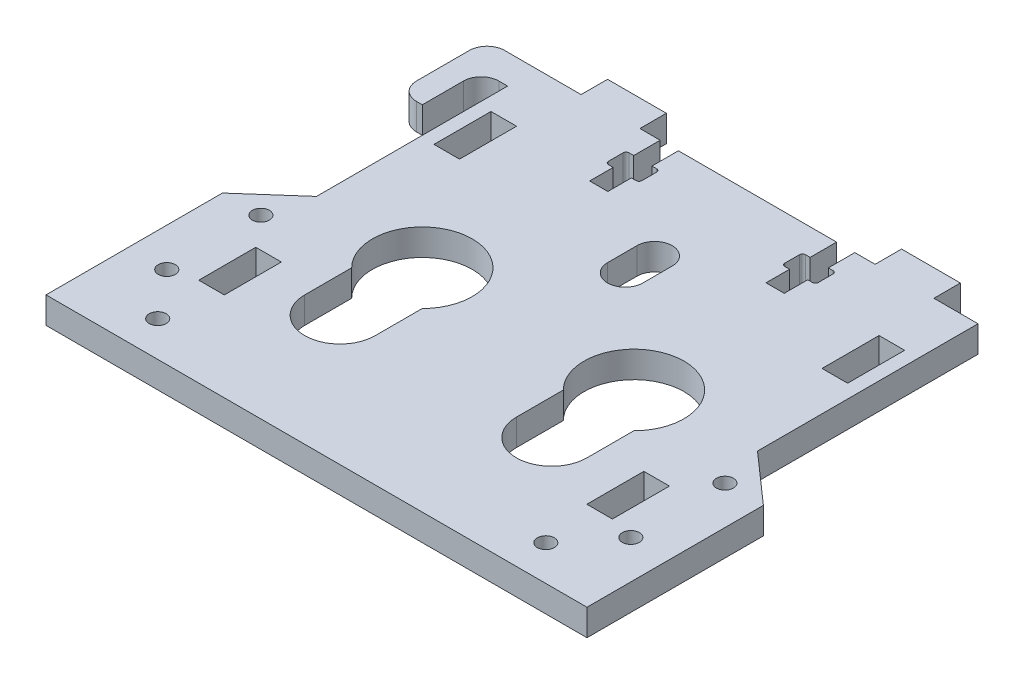
SolidWorks part; units mm, degrees
ref_plane "Front Plane" through (0, 0, 0) normal (0, 0, 1) x (1, 0, 0)
ref_plane "Top Plane" through (0, 0, 0) normal (0, 1, 0) x (1, 0, 0)
ref_plane "Right Plane" through (0, 0, 0) normal (1, 0, 0) x (0, 0, -1)
sketch "Sketch1" plane through (0, 0, 0) normal (0, 1, 0) x (1, 0, 0)
  line L1 (-37.5, 37.5) -> (37.5, 37.5)
  line L2 (-37.5, 37.5) -> (-37.5, -37.5)
  line L3 (-37.5, -37.5) -> (37.5, -37.5)
  line L4 (37.5, 37.5) -> (37.5, -37.5)
  line L5 (-37.5, 37.5) -> (37.5, -37.5) construction
  line L6 (-37.5, -37.5) -> (37.5, 37.5) construction
  point P0 (0, 0)
  dimension "D1" = 75
  dimension "D2" = 75
extrude "MainShape" add sketch "Sketch1" along normal blind 4.5
sketch "Sketch2" plane through (0, 4.5, 0) normal (0, 1, 0) x (1, 0, 0)
  line L0 (0, -37.5) -> (0, 37.5) construction
  line L1 (-37.5, -37.5) -> (37.5, -37.5) construction
  line L2 (37.5, 37.5) -> (-37.5, 37.5) construction
  line L4 (-5, 42) -> (5, 42)
  line L5 (-5, 42) -> (-5, 33)
  line L6 (-5, 33) -> (5, 33)
  line L7 (5, 42) -> (5, 33)
  line L8 (-5, 42) -> (5, 33) construction
  line L9 (-5, 33) -> (5, 42) construction
  dimension "D1" = 10
  dimension "D2" = 4.5
extrude "Tab1" [suppressed] add sketch "Sketch2" against normal through all
sketch "Sketch4" [suppressed] plane through (0, 4.5, 0) normal (0, 1, 0) x (1, 0, 0)
  line L0 (0, 42) -> (0, -37.5) construction
  line L1 (5, 42) -> (-5, 42) construction
  line L2 (-47.5, -37.5) -> (47.5, -37.5) construction
  line L3 (-40, 37.5) -> (-40, 27) construction
  line L4 (-5, 37.5) -> (-47.5, 37.5) construction
  line L5 (-38.25, 27) -> (-41.75, 27) construction
  line L6 (-41.75, 27) -> (-41.75, 37.5) construction
  line L7 (-38.25, 27) -> (-41.75, 27)
  line L8 (-41.75, 27) -> (-41.75, 29.5)
  line L9 (-41.75, 29.5) -> (-42.75, 29.5)
  line L10 (-43, 29.75) -> (-43, 33.45)
  line L11 (-42.75, 33.7) -> (-41.75, 33.7)
  line L12 (-41.75, 33.7) -> (-41.75, 37.5)
  line L13 (-41.75, 37.5) -> (-38.25, 37.5)
  line L14 (-38.25, 27) -> (-38.25, 37.5) construction
  line L15 (-38.25, 33.7) -> (-38.25, 37.5)
  line L16 (-37.25, 33.7) -> (-38.25, 33.7)
  line L17 (-37, 29.75) -> (-37, 33.45)
  line L18 (-38.25, 29.5) -> (-37.25, 29.5)
  line L19 (-38.25, 27) -> (-38.25, 29.5)
  line L20 (38.25, 27) -> (38.25, 37.5) construction
  line L21 (41.75, 27) -> (41.75, 37.5) construction
  line L22 (38.25, 27) -> (41.75, 27) construction
  line L23 (40, 37.5) -> (40, 27) construction
  line L24 (38.25, 27) -> (38.25, 29.5)
  line L25 (38.25, 29.5) -> (37.25, 29.5)
  line L26 (37, 29.75) -> (37, 33.45)
  line L27 (37.25, 33.7) -> (38.25, 33.7)
  line L28 (38.25, 33.7) -> (38.25, 37.5)
  line L29 (41.75, 37.5) -> (38.25, 37.5)
  line L30 (41.75, 33.7) -> (41.75, 37.5)
  line L31 (42.75, 33.7) -> (41.75, 33.7)
  line L32 (43, 29.75) -> (43, 33.45)
  line L33 (41.75, 29.5) -> (42.75, 29.5)
  line L34 (41.75, 27) -> (41.75, 29.5)
  line L35 (38.25, 27) -> (41.75, 27)
  arc A0 (-42.75, 29.5) -> (-43, 29.75) centre (-42.75, 29.75) cw
  arc A1 (-37, 29.75) -> (-37.25, 29.5) centre (-37.25, 29.75) cw
  arc A2 (-37.25, 33.7) -> (-37, 33.45) centre (-37.25, 33.45) cw
  arc A3 (-43, 33.45) -> (-42.75, 33.7) centre (-42.75, 33.45) cw
  arc A4 (43, 33.45) -> (42.75, 33.7) centre (42.75, 33.45) ccw
  arc A5 (37.25, 33.7) -> (37, 33.45) centre (37.25, 33.45) ccw
  arc A6 (37, 29.75) -> (37.25, 29.5) centre (37.25, 29.75) ccw
  arc A7 (42.75, 29.5) -> (43, 29.75) centre (42.75, 29.75) ccw
  point P24 (-43, 29.5)
  point P27 (-37, 29.5)
  point P30 (-37, 33.7)
  point P33 (-43, 33.7)
  point P56 (43, 33.7)
  point P57 (37, 33.7)
  point P58 (37, 29.5)
  point P59 (43, 29.5)
  dimension "D7" = 0.5
  dimension "D1" = 11
  dimension "D2" = 1.55
  dimension "D3" = 3.5
  dimension "D4" = 2.85
  dimension "D5" = 8
  dimension "D6" = 40
extrude "Cut-Extrude2" [suppressed] cut sketch "Sketch4" against normal through all
sketch "Sketch5" plane through (0, 4.5, 0) normal (0, 1, 0) x (1, 0, 0)
  line L0 (0, -37.5) -> (0, 37.5) construction
  line L1 (-37.5, -37.5) -> (37.5, -37.5) construction
  line L3 (33, 37.5) -> (33, -37.5) construction
  line L4 (37.5, 37.5) -> (-37.5, 37.5) construction
  line L5 (-33, 37.5) -> (-33, -37.5) construction
  line L6 (30.825, 27.35) -> (35.175, 27.35)
  line L7 (30.825, 27.35) -> (30.825, 17.65)
  line L8 (30.825, 17.65) -> (35.175, 17.65)
  line L9 (35.175, 27.35) -> (35.175, 17.65)
  line L10 (30.825, 27.35) -> (35.175, 17.65) construction
  line L11 (30.825, 17.65) -> (35.175, 27.35) construction
  line L12 (-30.825, 17.65) -> (-35.175, 27.35) construction
  line L13 (-30.825, 27.35) -> (-35.175, 17.65) construction
  line L14 (-35.175, 27.35) -> (-35.175, 17.65)
  line L15 (-30.825, 17.65) -> (-35.175, 17.65)
  line L16 (-30.825, 27.35) -> (-30.825, 17.65)
  line L17 (-30.825, 27.35) -> (-35.175, 27.35)
  line L18 (-37.5, 2.5) -> (37.5, 2.5) construction
  line L19 (-37.5, 37.5) -> (-37.5, -37.5) construction
  line L20 (37.5, -37.5) -> (37.5, 37.5) construction
  line L21 (-30.825, -22.35) -> (-35.175, -12.65) construction
  line L22 (-30.825, -12.65) -> (-35.175, -22.35) construction
  line L23 (30.825, -12.65) -> (35.175, -22.35) construction
  line L24 (30.825, -22.35) -> (35.175, -12.65) construction
  line L25 (-30.825, -22.35) -> (-35.175, -22.35)
  line L26 (-30.825, -22.35) -> (-30.825, -12.65)
  line L27 (-30.825, -12.65) -> (-35.175, -12.65)
  line L28 (-35.175, -22.35) -> (-35.175, -12.65)
  line L29 (35.175, -22.35) -> (35.175, -12.65)
  line L30 (30.825, -12.65) -> (35.175, -12.65)
  line L31 (30.825, -22.35) -> (30.825, -12.65)
  line L32 (30.825, -22.35) -> (35.175, -22.35)
  line L33 (-30.825, 27.35) -> (-35.175, 17.65) construction
  line L34 (-37.5, 37.5) -> (37.5, 37.5) construction
  line L35 (37.5, 37.5) -> (-37.5, 37.5) construction
  point P10 (33, 22.5)
  point P21 (-33, 22.5)
  point P36 (-33, -17.5)
  point P37 (33, -17.5)
  dimension "D1" = 33
  dimension "D2" = 9.7
  dimension "D3" = 4.35
  dimension "D4" = 15
  dimension "D5" = 40
extrude "Cut-Extrude3" cut sketch "Sketch5" against normal through all
sketch "Sketch6" plane through (0, 4.5, 0) normal (0, 1, 0) x (1, 0, 0)
  line L0 (-18, -37.5) -> (-18, 28) construction
  line L1 (-24, -15.5) -> (-24, -7.5208)
  line L3 (-37.5, -15.5) -> (37.5, -15.5) construction
  line L4 (-37.5, 37.5) -> (-37.5, -37.5) construction
  line L5 (37.5, -37.5) -> (37.5, 37.5) construction
  line L6 (37.5, 37.5) -> (-37.5, 37.5) construction
  line L7 (-37.5, -37.5) -> (37.5, -37.5) construction
  line L8 (-12, -15.5) -> (-12, -7.5208)
  line L9 (-37.5, 37.5) -> (37.5, 37.5) construction
  arc A0 (-24, -15.5) -> (-12, -15.5) centre (-18, -15.5) ccw
  arc A2 (-12, -7.5208) -> (-24, -7.5208) centre (-18, -1.5) ccw
  dimension "D1" = 12
  dimension "D6" = 8.5
  dimension "D2" = 53
  dimension "D3" = 0
  dimension "D5" = 0
  dimension "D7" = 14
  dimension "D4" = 18
extrude "Cut-Extrude4" cut sketch "Sketch6" against normal through all
sketch "Sketch13" plane through (0, 4.5, 0) normal (0, 1, 0) x (1, 0, 0)
  line L0 (-37.5, 0) -> (-46, -7.5)
  line L1 (-37.5, 37.5) -> (-37.5, -37.5) construction
  line L2 (-46, -7.5) -> (-46, -37.5)
  line L3 (-46, -37.5) -> (-37.5, -37.5)
  line L4 (-37.5, -37.5) -> (-37.5, 0)
  line L5 (0, 37.5) -> (0, -37.5) construction
  line L6 (37.5, 37.5) -> (-37.5, 37.5) construction
  line L7 (-37.5, -37.5) -> (37.5, -37.5) construction
  line L8 (37.5, -37.5) -> (37.5, 0)
  line L9 (46, -37.5) -> (37.5, -37.5)
  line L10 (46, -7.5) -> (46, -37.5)
  line L11 (37.5, 0) -> (46, -7.5)
  line L12 (-37.5, -37.5) -> (-37.5, 0)
  line M23 (37.5, -37.5) -> (37.5, 37.5)
  line M25 (-37.5, 37.5) -> (-37.5, -37.5)
  dimension "D1" = 46
  dimension "D2" = 30
extrude "Boss-Extrude2" add sketch "Sketch13" against normal through all contours L2 L3 L0 M25 | L11 L9 L10 M23 region at (-41.5926, 4.5, 20.5556) region at (41.5926, 4.5, 20.5556)
sketch "Sketch8" plane through (0, 4.5, 0) normal (0, 1, 0) x (1, 0, 0)
  line L0 (-18, -9.5) -> (-18, -21.5) construction
  line L1 (-18, -15.5) -> (-39.46, -15.5) construction
  line L2 (-39.46, -23.5) -> (-39.46, -7.5) construction
  line L3 (-18, -21.5) -> (-18, -9.5) construction
  circle A0 centre (-39.46, -7.5) radius 1.45
  circle A1 centre (-18, -15.5) radius 6 construction
  circle A2 centre (-39.46, -23.5) radius 1.45
  dimension "D3" = 2.9
  dimension "D1" = 0
  dimension "D2" = 8
  dimension "D4" = 21.46
extrude "Cut-Extrude6" cut sketch "Sketch8" against normal through all
mirror "Mirror1" about plane through (0, 0, 0) normal (1, 0, 0) of "Cut-Extrude6", "Cut-Extrude4"
sketch "Sketch11" plane through (0, 4.5, 0) normal (0, 1, 0) x (1, 0, 0)
  line L0 (0, 37.5) -> (0, -37.5) construction
  line L1 (37.5, 37.5) -> (-37.5, 37.5) construction
  line L2 (-46, -37.5) -> (46, -37.5) construction
  line L3 (-25, 42) -> (-25, 37.5) construction
  line L4 (-30, 37.5) -> (-20, 37.5)
  line L5 (-30, 37.5) -> (-30, 42)
  line L6 (-30, 42) -> (-20, 42)
  line L7 (-20, 37.5) -> (-20, 42)
  line L8 (25, 42) -> (25, 37.5) construction
  line L9 (20, 37.5) -> (20, 42)
  line L10 (30, 42) -> (20, 42)
  line L11 (30, 37.5) -> (30, 42)
  line L12 (30, 37.5) -> (20, 37.5)
  dimension "D1" = 10
  dimension "D2" = 4.5
  dimension "D3" = 25
extrude "RearTabs" add sketch "Sketch11" against normal through all
sketch "Sketch12" plane through (0, 4.5, 0) normal (0, 1, 0) x (1, 0, 0)
  line L0 (-15, 0) -> (-15, 37.5) construction
  line L1 (20, 37.5) -> (-20, 37.5) construction
  line L2 (-13.45, 37.5) -> (-16.55, 37.5)
  line L3 (-16.55, 37.5) -> (-16.55, 33)
  line L4 (-16.55, 33) -> (-17.35, 33)
  line L5 (-17.85, 32.5) -> (-17.85, 30)
  line L6 (-17.35, 29.5) -> (-16.55, 29.5)
  line L7 (-16.55, 29.5) -> (-16.55, 25.5)
  line L8 (-16.55, 25.5) -> (-13.45, 25.5)
  line L9 (-13.45, 29.5) -> (-13.45, 25.5)
  line L10 (-12.65, 29.5) -> (-13.45, 29.5)
  line L11 (-12.15, 32.5) -> (-12.15, 30)
  line L12 (-13.45, 33) -> (-12.65, 33)
  line L13 (-13.45, 37.5) -> (-13.45, 33)
  line L14 (0, 37.5) -> (0, 23.4067) construction
  line L15 (13.45, 37.5) -> (13.45, 33)
  line L16 (13.45, 33) -> (12.65, 33)
  line L17 (12.15, 32.5) -> (12.15, 30)
  line L18 (12.65, 29.5) -> (13.45, 29.5)
  line L19 (13.45, 29.5) -> (13.45, 25.5)
  line L20 (16.55, 25.5) -> (13.45, 25.5)
  line L21 (16.55, 29.5) -> (16.55, 25.5)
  line L22 (17.35, 29.5) -> (16.55, 29.5)
  line L23 (17.85, 32.5) -> (17.85, 30)
  line L24 (16.55, 33) -> (17.35, 33)
  line L25 (16.55, 37.5) -> (16.55, 33)
  line L26 (13.45, 37.5) -> (16.55, 37.5)
  arc A0 (-17.85, 30) -> (-17.35, 29.5) centre (-17.35, 30) ccw
  arc A1 (-17.35, 33) -> (-17.85, 32.5) centre (-17.35, 32.5) ccw
  arc A2 (-12.65, 33) -> (-12.15, 32.5) centre (-12.65, 32.5) cw
  arc A3 (-12.15, 30) -> (-12.65, 29.5) centre (-12.65, 30) cw
  arc A4 (12.15, 30) -> (12.65, 29.5) centre (12.65, 30) ccw
  arc A5 (12.65, 33) -> (12.15, 32.5) centre (12.65, 32.5) ccw
  arc A6 (17.35, 33) -> (17.85, 32.5) centre (17.35, 32.5) cw
  arc A7 (17.85, 30) -> (17.35, 29.5) centre (17.35, 30) cw
  point P14 (-17.85, 29.5)
  point P17 (-17.85, 33)
  point P25 (-15, 25.5)
  point P28 (-12.15, 33)
  point P29 (-12.15, 29.5)
  point P53 (12.15, 29.5)
  point P54 (12.15, 33)
  point P55 (15, 25.5)
  point P56 (17.85, 33)
  point P57 (17.85, 29.5)
  dimension "D5" = 8
  dimension "D1" = 12
  dimension "D6" = 0.5
  dimension "D2" = 3.5
  dimension "D3" = 2.85
  dimension "D4" = 1.55
  dimension "D7" = 15
extrude "FrontScrewSlot" cut sketch "Sketch12" against normal through all
sketch "Sketch14" plane through (0, 4.5, 0) normal (0, 1, 0) x (1, 0, 0)
  line L0 (-33, 27.35) -> (-33, -37.5) construction
  line L1 (-30.825, 27.35) -> (-35.175, 27.35) construction
  line L2 (-46, -37.5) -> (46, -37.5) construction
  line L3 (-30, 37.5) -> (-37.5, 37.5) construction
  line L4 (0, 0) -> (0, -37.5) construction
  line L5 (33, 27.35) -> (33, -37.5) construction
  line L6 (-33, 27.35) -> (-33, -37.5) construction
  circle A0 centre (-33, -31.5) radius 1.45
  circle A1 centre (33, -31.5) radius 1.45
  dimension "D2" = 2.9
  dimension "D1" = 69
extrude "BraceScrews" cut sketch "Sketch14" against normal through all
sketch "Sketch15" plane through (0, 4.5, 0) normal (0, 1, 0) x (1, 0, 0)
  line L0 (0, -37.5) -> (0, 27.5) construction
  line L1 (-46, -37.5) -> (46, -37.5) construction
  line L3 (16, 27.5) -> (-16, 27.5) construction
  line L4 (-16.55, 37.5) -> (-20, 37.5) construction
  line L5 (-18.175, 32.35) -> (-13.825, 32.35)
  line L6 (-18.175, 32.35) -> (-18.175, 22.65)
  line L7 (-18.175, 22.65) -> (-13.825, 22.65)
  line L8 (-13.825, 32.35) -> (-13.825, 22.65)
  line L9 (-18.175, 32.35) -> (-13.825, 22.65) construction
  line L10 (-18.175, 22.65) -> (-13.825, 32.35) construction
  line L11 (18.175, 22.65) -> (13.825, 32.35) construction
  line L12 (18.175, 32.35) -> (13.825, 22.65) construction
  line L13 (13.825, 32.35) -> (13.825, 22.65)
  line L14 (18.175, 22.65) -> (13.825, 22.65)
  line L15 (18.175, 32.35) -> (18.175, 22.65)
  line L16 (18.175, 32.35) -> (13.825, 32.35)
  point P19 (0, 27.5)
  dimension "D1" = 16
  dimension "D2" = 4.35
  dimension "D3" = 9.7
  dimension "D4" = 10
extrude "FanTabs" [suppressed] cut sketch "Sketch15" against normal through all
sketch "Sketch16" plane through (0, 4.5, 0) normal (0, 1, 0) x (1, 0, 0)
  line L0 (0, 0) -> (0, 37.5) construction
  line L2 (0, 20) -> (0, 15) construction
  line L3 (3, 20) -> (3, 15)
  line L4 (-3, 20) -> (-3, 15)
  line L5 (13.45, 37.5) -> (-13.45, 37.5) construction
  arc A0 (3, 20) -> (-3, 20) centre (0, 20) ccw
  arc A1 (-3, 15) -> (3, 15) centre (0, 15) ccw
  point P7 (0, 17.5)
  dimension "D1" = 3
  dimension "D2" = 20
  dimension "D3" = 5
extrude "WiringSlot" cut sketch "Sketch16" against normal through all
sketch "Sketch17" [suppressed] plane through (0, 4.5, 0) normal (0, 1, 0) x (1, 0, 0)
  line L0 (-37.5, 14.5) -> (-37.5, 10.5) construction
  line L3 (-37.5, 37.5) -> (-37.5, 0) construction
  line L4 (-36, 14.5) -> (-36, 10.5)
  line L5 (-39, 14.5) -> (-39, 10.5)
  line L6 (-37.5, 14.5) -> (-37.5, 10.5) construction
  line L7 (-34, 14.5) -> (-34, 10.5)
  line L8 (-41, 14.5) -> (-41, 10.5)
  line L9 (-41, 12.5) -> (-37.5, 12.5) construction
  line L10 (0, 0) -> (0, -12.1805) construction
  arc A0 (-36, 14.5) -> (-39, 14.5) centre (-37.5, 14.5) ccw
  arc A1 (-39, 10.5) -> (-36, 10.5) centre (-37.5, 10.5) ccw
  arc A2 (-34, 14.5) -> (-41, 14.5) centre (-37.5, 14.5) ccw
  arc A3 (-41, 10.5) -> (-34, 10.5) centre (-37.5, 10.5) ccw
  point P4 (-37.5, 12.5)
  point P10 (-37.5, 12.5)
  dimension "D4" = 4
  dimension "D5" = 25
  dimension "D1" = 0
  dimension "D2" = 2
  dimension "D3" = 1.5
extrude "Boss-Extrude3" [suppressed] add sketch "Sketch17" against normal through all
mirror "Mirror2" [suppressed] about plane through (0, 0, 0) normal (1, 0, 0)
sketch "Sketch18" [suppressed] plane through (0, 4.5, 0) normal (0, 1, 0) x (1, 0, 0)
  line L0 (0, -37.5) -> (0, 47.6111) construction
  line L1 (-45, -37.5) -> (45, -37.5) construction
  line L2 (-12, 2) -> (-12, -19.46) construction
  line L3 (-4, -19.46) -> (-20, -19.46) construction
  circle A0 centre (-12, 2) radius 5
  circle A1 centre (-20, -19.46) radius 1.45
  circle A2 centre (-4, -19.46) radius 1.45
  dimension "D2" = 8
  dimension "D4" = 21.46
  dimension "D1" = 2.9
  dimension "D3" = 10
  dimension "D5" = 12
  dimension "D6" = 2
extrude "Cut-Extrude7" [suppressed] cut sketch "Sketch18" against normal through all
mirror "Mirror3" [suppressed] about plane through (0, 0, 0) normal (1, 0, 0)
sketch "Sketch19" [suppressed] plane through (0, 4.5, 0) normal (0, 1, 0) x (1, 0, 0)
  line L0 (-17, 2) -> (-7, 2) construction
  line L1 (-12, 2) -> (-4, 2) construction
  line L2 (-12, 4) -> (-4, 4)
  line L3 (-12, 0) -> (-4, 0)
  line L4 (-12, 7) -> (-12, -3) construction
  line L5 (0, 0) -> (0, 6.8806) construction
  line L6 (12, 7) -> (12, -3) construction
  line L7 (17, 2) -> (7, 2) construction
  line L8 (12, 2) -> (4, 2) construction
  line L9 (12, 4) -> (4, 4)
  line L10 (12, 0) -> (4, 0)
  circle A0 centre (-12, 2) radius 5 construction
  arc A1 (-12, 4) -> (-12, 0) centre (-12, 2) ccw
  arc A2 (-4, 0) -> (-4, 4) centre (-4, 2) ccw
  arc A3 (12, 4) -> (12, 0) centre (12, 2) cw
  arc A4 (4, 0) -> (4, 4) centre (4, 2) cw
  point P6 (-8, 2)
  point P23 (8, 2)
  dimension "D1" = 2
  dimension "D2" = 8
extrude "Cut-Extrude8" [suppressed] cut sketch "Sketch19" against normal through all
sketch "Sketch20" plane through (0, 4.5, 0) normal (0, 1, 0) x (1, 0, 0)
  line L0 (0, 0) -> (0, -37.5) construction
  line L1 (-46, -37.5) -> (46, -37.5) construction
  line L2 (-26.9758, -32.9017) -> (-26.9758, -26.6196)
  line L3 (-26.9758, -26.6196) -> (-6.5592, -26.6196)
  line L4 (-6.5592, -26.6196) -> (-6.5592, 9.4097)
  line L5 (-6.5592, 9.4097) -> (6.5592, 9.4097)
  line L6 (-26.9758, -32.9017) -> (26.9758, -32.9017)
  line L7 (6.5592, -26.6196) -> (6.5592, 9.4097)
  line L8 (26.9758, -26.6196) -> (6.5592, -26.6196)
  line L9 (26.9758, -32.9017) -> (26.9758, -26.6196)
  point P12 (0, -32.9017)
  point P13 (0, 9.4097)
extrude "Cut-Extrude9" [suppressed] cut sketch "Sketch20" against normal through all
sketch "Sketch21" plane through (0, 4.5, 0) normal (0, 1, 0) x (1, 0, 0)
  line L0 (-46, -37.5) -> (-46, 37.5) construction
  line L1 (-37, 37.5) -> (-43, 37.5)
  line L4 (-46, 34.5) -> (-46, 25.5)
  line L5 (-43, 22.5) -> (-42, 22.5)
  line L6 (-42, 22.5) -> (-42, 29.5)
  line L7 (-39, 32.5) -> (-37, 32.5)
  line L9 (-37, 32.5) -> (-37, 37.5)
  line L10 (-30, 37.5) -> (-37.5, 37.5) construction
  line L11 (-37.5, 37.5) -> (-37.5, 0) construction
  arc A0 (-42, 29.5) -> (-39, 32.5) centre (-39, 29.5) cw
  arc A1 (-46, 25.5) -> (-43, 22.5) centre (-43, 25.5) ccw
  arc A2 (-43, 37.5) -> (-46, 34.5) centre (-43, 34.5) ccw
  point P19 (-46, 22.5)
  point P24 (-42, 37.5)
  dimension "D1" = 3
  dimension "D4" = 3
  dimension "D2" = 15
  dimension "D3" = 5
  dimension "D5" = 4
  dimension "D6" = 0.5
  dimension "D7" = 0
extrude "Boss-Extrude4" add sketch "Sketch21" against normal through all
sketch "Sketch22" plane through (0, 4.5, 0) normal (0, 1, 0) x (1, 0, 0)
  line L0 (-46, -7.5) -> (-46, 13.5)
  line L1 (-43, 16.5) -> (-42, 16.5)
  line L2 (-42, 16.5) -> (-42, -3.9706)
  line L3 (-37.5, 0) -> (-46, -7.5) construction
  line L4 (-42, -3.9706) -> (-46, -7.5)
  line L5 (-46, 16.5) -> (-46, 28.3122) construction
  line L6 (-46, 34.5) -> (-46, 25.5) construction
  line L7 (-42, 22.6875) -> (-42, 12.0504) construction
  line L8 (-42, 22.5) -> (-42, 29.5) construction
  arc A0 (-46, 13.5) -> (-43, 16.5) centre (-43, 13.5) cw
  dimension "D2" = 3
  dimension "D1" = 6
extrude "Boss-Extrude5" [suppressed] add sketch "Sketch22" against normal through all
mirror "Mirror6" [suppressed] about plane through (0, 0, 0) normal (1, 0, 0)
equation "\"X-ROD-SPACING\"=45"
equation "\"Y-ROD-SPACING\"=75"
equation "\"Z-ROD-SPACING\"=17.5"
equation "\"Y-BED-OFFSET\"=2"
equation "\"Y-BED-ROD-INSET\"=3.5"
equation "\"Y-BED-SCREW-SPACING\"=209"
equation "\"Y-BED-SCREW-CUTOUT-SLOT-HEIGHT\"=2"
equation "\"T-SLOT-NUT-FILLET-RADIUS\"=0.5"
equation "\"T-SLOT-SCREW-SHAFT-RADIUS\"=1.55"
equation "\"T-SLOT-SCREW-SHAFT-CUTOUT-LENGTH\"=11"
equation "\"T-SLOT-NUT-DEPTH\"=3.5"
equation "\"T-SLOT-NUT-WIDTH\"=2.85"
equation "\"T-SLOT-NUT-END-DISTANCE\"=8"
equation "\"ACRYLIC-THICKNESS\"=10"
equation "\"ACRYLIC-THICKNESS2\"=4.5"
equation "\"ACRYLIC-TAB-CUTOUT-SIZE\"=\"ACRYLIC-THICKNESS\"+\"ACRYLIC-TAB-TOLERANCE\"*2"
equation "\"ACRYLIC-TAB-WIDTH\"=\"ACRYLIC-THICKNESS\""
equation "\"ACRYLIC-M3-HOLE\"=2.9"
equation "\"SMOOTHROD-CAP-SCREW-DISTANCE\"=20"
equation "\"FRAME-WIDTH-INNER\"=370"
equation "\"NEMA17-HOLE-SPACING\"=31"
equation "\"NEMA17-CENTRAL-CUTOUT\"=22.5"
equation "\"Z-BRACKET-REACH\"=57"
equation "\"Z-ROD-INSET\"=13.5"
equation "\"TOP-BRACKET-SPACING\"=40"
equation "\"SMOOTHROD-X-LENGTH\"=350"
equation "\"SMOOTHROD-Y-LENGTH\"=350"
equation "\"SMOOTHROD-Z-LENGTH\"=350"
equation "\"SMOOTHROD-TIGHTENING-HEADROOM\"=.25"
equation "\"LEADSCREW-Z-LENGTH\"=300"
equation "\"SCREW-LENGTH-FRAME\"=\"ACRYLIC-THICKNESS\" + 10"
equation "\"SCREW-LENGTH-MOTOR\"=\"ACRYLIC-THICKNESS\" + 5"
equation "\"SCREW-LENGTH-EXTRUDER\"=28"
equation "\"SCREW-HEAD-RADIUS\"=6"
equation "\"PRINTED-X-SMOOTHROD-DIAMETER\"=8.8"
equation "\"PRINTED-X-SMOOTHROD-CUTOUT\"=10"
equation "\"PRINTED-X-BASE-HEIGHT\"=10"
equation "\"PRINTED-LM8UU-CUTOUT-SIZE\"=15.5"
equation "\"PRINTED-LM8UU-CUTOUT-LENGTH\"=24.5"
equation "\"PRINTED-X-IDLER-HEIGHT\"=16"
equation "\"PSU-MOUNTING-WIDTH\"=95"
equation "\"PSU-MOUNTING-HEIGHT\"=177"
equation "\"Y-BELT-TO-ROD-DISTANCE\"=20"
equation "\"SPOOL-HOLDER-ROD-SPACING\"=150"
equation "\"ACRYLIC-X-CARRIAGE-WIDTH\"=55"
equation "\"ACRYLIC-X-CARRIAGE-HEIGHT\"=75"
equation "\"ACRYLIC-X-CARRIAGE-SCREW-SPACING-X\"=15"
equation "\"ACRYLIC-X-CARRIAGE-SCREW-SPACING-Y\"=33"
equation "\"ACRYLIC-X-CARRIAGE-CENTER-TAB-SPACING\"=14"
equation "\"D1@MainShape\" = \"ACRYLIC-THICKNESS2\""
equation "\"D1@Sketch2\"=\"ACRYLIC-TAB-WIDTH\""
equation "\"D2@Sketch2\"=\"ACRYLIC-THICKNESS2\""
equation "\"D1@Sketch4\"=\"T-SLOT-SCREW-SHAFT-CUTOUT-LENGTH\""
equation "\"D2@Sketch4\"=\"T-SLOT-SCREW-SHAFT-RADIUS\""
equation "\"D3@Sketch4\"=\"T-SLOT-NUT-DEPTH\""
equation "\"D4@Sketch4\"=\"T-SLOT-NUT-WIDTH\""
equation "\"D5@Sketch4\"=\"T-SLOT-NUT-END-DISTANCE\""
equation "\"D7@Sketch4\"=\"T-SLOT-NUT-FILLET-RADIUS\""
equation "\"ACRYLIC-X-CARRIAGE-EXTRUDER-SHELF-DEPTH\"=\"ACRYLIC-X-CARRIAGE-EXTRUDER-OFFSET\" + 28"
equation "\"ACRYLIC-X-CARRIAGE-LM8UU-CUTOUT-WIDTH\"=24.25"
equation "\"ACRYLIC-X-CARRIAGE-EXTRUDER-BRACE-SPACING\"=23"
equation "\"ACRYLIC-X-CARRIAGE-EXTRUDER-BRACE-TAB-OFFSET\"=20"
equation "\"ACRYLIC-X-CARRIAGE-EXTRUDER-BRACE-HEIGHT\"=35"
equation "\"ACRYLIC-X-CARRIAGE-EXTRUDER-BRACE-SCREW-SPACING\"=22"
equation "\"D2@Sketch5\"=\"ACRYLIC-THICKNESS2-TAB-CUTOUT-HEIGHT\""
equation "\"D3@Sketch5\"=\"ACRYLIC-THICKNESS2-TAB-CUTOUT-WIDTH\""
equation "\"D3@Sketch8\"=\"ACRYLIC-M3-HOLE\""
equation "\"ACRYLIC-X-CARRIAGE-EXTRUDER-ANGLE\"=90"
equation "\"ACRYLIC-X-CARRIAGE-EXTRUDER-OFFSET\"=26"
equation "\"ACRYLIC-TAB-TOLERANCE\"=-.05"
equation "\"ACRYLIC-X-CARRIAGE-DUAL-WIDTH-MULTIPLIER\"=1.65"
equation "\"ACRYLIC-X-CARRIAGE-DUAL-HOTEND-SPACING\"=42"
equation "\"ACRYLIC-X-CARRIAGE-DUAL-WIDTH\"=75"
equation "\"ACRYLIC-X-CARRIAGE-DUAL-HOTEND-SEPARATION\"=36"
equation "\"ACRYLIC-X-CARRIAGE-DUAL-MOUNT-PLATE-DEPTH\"=75"
equation "\"ACRYLIC-X-CARRIAGE-DUAL-MOUNT-BRACE-WIDTH\"=33"
equation "\"D1@Sketch5\"=\"ACRYLIC-X-CARRIAGE-DUAL-MOUNT-BRACE-WIDTH\""
equation "\"ACRYLIC-X-CARRIAGE-DUAL-MOUNT-SCREW-WIDTH\"=40"
equation "\"D6@Sketch4\"=\"ACRYLIC-X-CARRIAGE-DUAL-MOUNT-SCREW-WIDTH\""
equation "\"D1@Sketch1\"=\"ACRYLIC-X-CARRIAGE-DUAL-WIDTH\""
equation "\"D2@Sketch1\"=\"ACRYLIC-X-CARRIAGE-DUAL-MOUNT-PLATE-DEPTH\""
equation "\"D4@Sketch6\"=\"ACRYLIC-X-CARRIAGE-DUAL-HOTEND-SEPARATION\"/2"
equation "\"D1@Sketch11\"=\"ACRYLIC-TAB-WIDTH\""
equation "\"D2@Sketch11\"=\"ACRYLIC-THICKNESS2\""
equation "\"D1@Sketch12\"=\"T-SLOT-SCREW-SHAFT-CUTOUT-LENGTH\"+1"
equation "\"D2@Sketch12\"=\"T-SLOT-NUT-DEPTH\""
equation "\"D3@Sketch12\"=\"T-SLOT-NUT-WIDTH\""
equation "\"D4@Sketch12\"=\"T-SLOT-SCREW-SHAFT-RADIUS\""
equation "\"D5@Sketch12\"=\"T-SLOT-NUT-END-DISTANCE\""
equation "\"D6@Sketch12\"=\"T-SLOT-NUT-FILLET-RADIUS\""
equation "\"D2@Sketch14\"=\"ACRYLIC-M3-HOLE\""
equation "\"D2@Sketch15\"=\"ACRYLIC-THICKNESS2-TAB-CUTOUT-WIDTH\""
equation "\"D3@Sketch15\"=\"ACRYLIC-THICKNESS2-TAB-CUTOUT-HEIGHT\""
equation "\"KERF\"=0.075"
equation "\"PRINTED-M3-HOLE\"=3.5"
equation "\"PRINTED-M3-NUT-AF\"=6.25"
equation "\"ACRYLIC-X-CARRIAGE-LM8UU-CUTOUT-HEIGHT\"=11.0"
equation "\"ACRYLIC-X-CARRIAGE-DUAL-FAN-OFFSET\"=52"
equation "\"ACRYLIC-X-CARRIAGE-DUAL-FAN-HEIGHT\"=20"
equation "\"BLOWER-FAN-WIDTH\"=15"
equation "\"ACRYLIC-THICKNESS-TAB-CUTOUT-WIDTH\"=\"ACRYLIC-THICKNESS\"-\"KERF\"*2"
equation "\"ACRYLIC-THICKNESS-TAB-CUTOUT-HEIGHT\"=\"ACRYLIC-TAB-WIDTH\"-\"KERF\"*4"
equation "\"ACRYLIC-THICKNESS2-TAB-CUTOUT-WIDTH\"=\"ACRYLIC-THICKNESS2\"-\"KERF\"*2"
equation "\"ACRYLIC-THICKNESS2-TAB-CUTOUT-HEIGHT\"=\"ACRYLIC-TAB-WIDTH\"-\"KERF\"*4"
equation "\"D1@Sketch18\"=\"ACRYLIC-M3-HOLE\""
equation "\"D7@Sketch12\"=\"ACRYLIC-X-CARRIAGE-SCREW-SPACING-X\""
